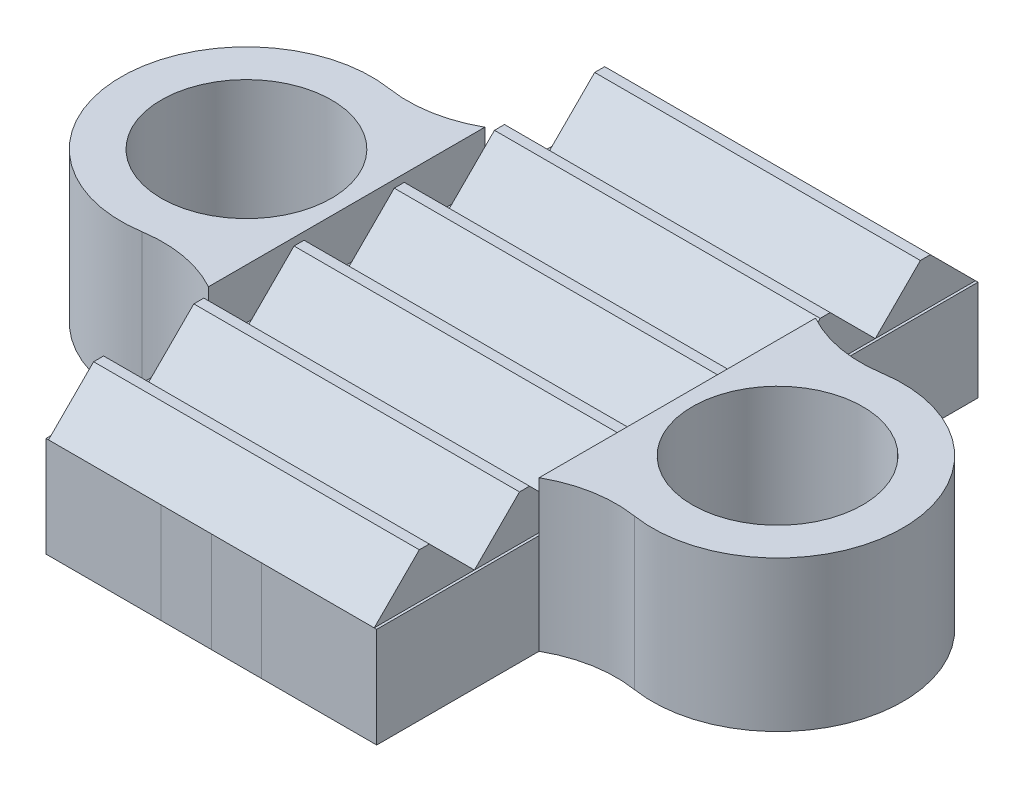
SolidWorks part; units mm, degrees
note: The reader was unsure of these and kept them because the rebuilt part matched: shared geometry of "Sketch1<3>", "Sketch1<4>", "Croquis1<4>".
ref_plane "Alzado" through (0, 0, 0) normal (0, 0, 1) x (1, 0, 0)
ref_plane "Planta" through (0, 0, 0) normal (0, 1, 0) x (1, 0, 0)
ref_plane "Vista lateral" through (0, 0, 0) normal (1, 0, 0) x (0, 0, -1)
sketch "Croquis1" plane through (0, 0, 0) normal (0, 1, 0) x (1, 0, 0)
  line L0 (0, -16.4018) -> (0, 78.9163) construction
  line L1 (-63.9099, 0) -> (63.9099, 0) construction
  line L2 (-3.3, 6) -> (3.3, 6)
  line L3 (3.3, 6) -> (3.3, 2.7581)
  line L4 (-3.3, -6) -> (3.3, -6)
  line L5 (3.3, -6) -> (3.3, -2.7581)
  line L6 (-3.3, -6) -> (-3.3, -2.7581)
  line L7 (-3.3, 6) -> (-3.3, 2.7581)
  line L8 (3.3, -2.7581) -> (3.3, 2.7581)
  line L9 (-3.3, -2.7581) -> (-3.3, 2.7581)
  circle A0 centre (5.3, 0) radius 1.7
  arc A1 (4.911, -2.4695) -> (4.911, 2.4695) centre (5.3, 0) ccw
  arc A2 (3.3, 2.7581) -> (4.911, 2.4695) centre (4.5219, 4.9391) ccw
  arc A3 (3.3, -2.7581) -> (4.911, -2.4695) centre (4.5219, -4.9391) cw
  arc A4 (-3.3, -2.7581) -> (-4.911, -2.4695) centre (-4.5219, -4.9391) ccw
  arc A5 (-3.3, 2.7581) -> (-4.911, 2.4695) centre (-4.5219, 4.9391) cw
  arc A6 (-4.911, -2.4695) -> (-4.911, 2.4695) centre (-5.3, 0) cw
  circle A7 centre (-5.3, 0) radius 1.7
  point P6 (7.8, 0)
  point P10 (8, 0)
  point P19 (0, 0)
  point P28 (0, -6)
  point P29 (-8, 0)
  point P30 (0, 6)
  dimension "D1" = 7.8
  dimension "D5" = 5
  dimension "D6" = 5
  dimension "D4" = 6
extrude "Saliente-Extruir1" add sketch "Croquis1" along normal blind 2 contours L9 L6 L4 L5 L8 L3 L2 L7 | L8 A3 A1 A2 A0 | A6 A4 L9 A5 A7
ref_plane "Plano1" through (3.25, 0, 0) normal (1, 0, 0) x (0, 0, -1)
sketch "Croquis4" plane through (3.25, 0, 0) normal (1, 0, 0) x (0, 0, -1)
  line L0 (-6, 2) -> (-4, 2)
  line L1 (-6, 2) -> (-5.1, 2.9)
  line L2 (-5, 3) -> (-5, 2) construction
  line L3 (-4, 2) -> (-4.9, 2.9)
  line L4 (-5.1, 2.9) -> (-4.9, 2.9)
  dimension "D1" = 1
  dimension "D2" = 1
  dimension "D3" = 0.9
extrude "Saliente-Extruir2" add sketch "Croquis4" against normal blind 6.5
pattern_linear "MatrizL1" count 6 spacing 2 along (0, 0, -1) of "Saliente-Extruir2"
sketch "Sketch1" plane through (0, 0, 6) normal (0, 0, 1) x (1, 0, 0)
  line L0 (0, 2) -> (0, 0)
  line L1 (-3.25, 2) -> (3.25, 2) construction
  line L4 (-1, 2) -> (1, 2)
  line L5 (-1, 2) -> (-1, 0)
  line L6 (-1, 0) -> (1, 0)
  line L7 (1, 2) -> (1, 0)
  dimension "D1" = 1
  dimension "D2" = 1
extrude "Cut-Extrude1" cut sketch "Sketch1" against normal blind 0.1
extrude "Boss-Extrude1" add sketch "Sketch1<3>" against normal blind 0.1 separate body
sketch "Sketch1<3>" plane through (0, 0, 6) normal (0, 0, 1) x (1, 0, 0) same geometry as "Sketch1"
extrude "Boss-Extrude2" add sketch "Sketch1<4>" against normal blind 0.1 separate body
sketch "Sketch1<4>" plane through (0, 0, 6) normal (0, 0, 1) x (1, 0, 0) same geometry as "Sketch1"
extrude "Boss-Extrude3" add sketch "Croquis1<4>" along normal blind 1 from surface at 2 contours A6 A4 L9 A5 A7 | L8 A3 A1 A2 A0 starting at face at (-5.3, 2, 1.7)
sketch "Croquis1<4>" plane through (0, 0, 0) normal (0, 1, 0) x (1, 0, 0) same geometry as "Croquis1"
